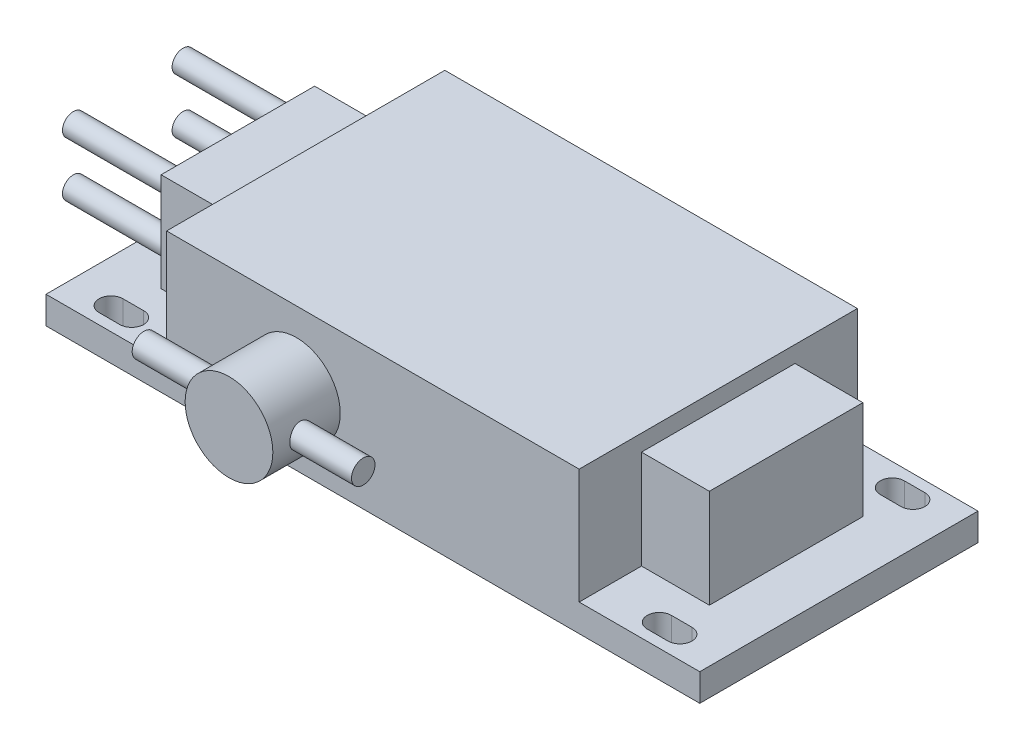
SolidWorks part; units mm, degrees
ref_plane "Спереди" through (0, 0, 0) normal (0, 0, 1) x (1, 0, 0)
ref_plane "Сверху" through (0, 0, 0) normal (0, 1, 0) x (1, 0, 0)
ref_plane "Справа" through (0, 0, 0) normal (1, 0, 0) x (0, 0, -1)
sketch "Sketch1" plane through (0, 0, 0) normal (0, 1, 0) x (1, 0, 0)
  line L0 (107.74, 21.25) -> (111.51, 21.25) construction
  line L1 (0, 25.375) -> (119.25, 25.375)
  line L2 (0, 25.375) -> (0, -25.375)
  line L3 (0, -25.375) -> (119.25, -25.375)
  line L4 (119.25, 25.375) -> (119.25, -25.375)
  line L5 (107.74, 23.435) -> (111.51, 23.435)
  line L6 (107.74, 19.065) -> (111.51, 19.065)
  line L7 (107.74, -21.25) -> (111.51, -21.25) construction
  line L8 (107.74, -19.065) -> (111.51, -19.065)
  line L9 (107.74, -23.435) -> (111.51, -23.435)
  line L10 (7.74, -21.25) -> (11.51, -21.25) construction
  line L11 (7.74, -19.065) -> (11.51, -19.065)
  line L12 (7.74, -23.435) -> (11.51, -23.435)
  line L13 (7.74, 21.25) -> (11.51, 21.25) construction
  line L14 (7.74, 23.435) -> (11.51, 23.435)
  line L15 (7.74, 19.065) -> (11.51, 19.065)
  line L16 (11.51, -21.25) -> (107.74, -21.25) construction
  line L17 (109.625, 21.25) -> (109.625, -21.25) construction
  arc A0 (107.74, 23.435) -> (107.74, 19.065) centre (107.74, 21.25) ccw
  arc A1 (111.51, 19.065) -> (111.51, 23.435) centre (111.51, 21.25) ccw
  arc A2 (107.74, -19.065) -> (107.74, -23.435) centre (107.74, -21.25) ccw
  arc A3 (111.51, -23.435) -> (111.51, -19.065) centre (111.51, -21.25) ccw
  arc A4 (7.74, -19.065) -> (7.74, -23.435) centre (7.74, -21.25) ccw
  arc A5 (11.51, -23.435) -> (11.51, -19.065) centre (11.51, -21.25) ccw
  arc A6 (7.74, 23.435) -> (7.74, 19.065) centre (7.74, 21.25) ccw
  arc A7 (11.51, 19.065) -> (11.51, 23.435) centre (11.51, 21.25) ccw
  point P5 (0, 0)
  point P8 (109.625, 21.25)
  point P13 (109.625, -21.25)
  point P20 (9.625, -21.25)
  point P27 (9.625, 21.25)
  point P36 (59.625, -21.25)
  point P37 (59.625, -25.375)
  point P38 (109.625, 0)
  point P39 (119.25, 0)
  point P42 (5.555, 21.25)
  point P43 (13.695, 21.25)
  dimension "D1" = 119.25
  dimension "D2" = 50.75
  dimension "D3" = 100
  dimension "D4" = 42.5
  dimension "D5" = 4.37
  dimension "D6" = 8.14
extrude "Extrude1" add sketch "Sketch1" along normal blind 5
sketch "Sketch2" plane through (0, 5, 0) normal (0, 1, 0) x (1, 0, 0)
  line L0 (119.25, 25.375) -> (0, 25.375) construction
  line L1 (22, 25.375) -> (97.25, 25.375)
  line L2 (22, 25.375) -> (22, -25.375)
  line L3 (22, -25.375) -> (97.25, -25.375)
  line L4 (97.25, 25.375) -> (97.25, -25.375)
  line L5 (0, -25.375) -> (119.25, -25.375) construction
  line L6 (0, 0) -> (119.25, 0) construction
  line L7 (119.25, -25.375) -> (119.25, 25.375) construction
  line L9 (22, -25.375) -> (97.25, 25.375) construction
  point P14 (59.625, 0)
  point P15 (59.625, 0)
  dimension "D1" = 22
extrude "Extrude2" add sketch "Sketch2" along normal blind 21
sketch "Sketch3" plane through (0, 5, 0) normal (0, 1, 0) x (1, 0, 0)
  line L0 (97.25, 25.375) -> (22, -25.375) construction
  line L1 (109.625, -14) -> (9.625, -14)
  line L2 (109.625, -14) -> (109.625, 14)
  line L3 (109.625, 14) -> (9.625, 14)
  line L4 (9.625, -14) -> (9.625, 14)
  line L5 (109.625, -14) -> (9.625, 14) construction
  point P9 (59.625, 0)
  point P10 (59.625, 0)
  dimension "D1" = 100
  dimension "D2" = 28
extrude "Extrude3" add sketch "Sketch3" along normal blind 18
sketch "Sketch4" plane through (0, 0, 25.375) normal (0, 0, 1) x (1, 0, 0)
  line L0 (45.6774, 0) -> (45.6774, 26) construction
  line L1 (0, 0) -> (119.25, 0) construction
  line L2 (22, 26) -> (97.25, 26) construction
  circle A0 centre (45.6774, 13) radius 8
  point P9 (45.6774, 13)
  dimension "D1" = 16
extrude "Extrude4" add sketch "Sketch4" along normal blind 12.3
sketch "Sketch5" plane through (97.25, 0, 0) normal (1, 0, 0) x (0, 0, -1)
  line L0 (-36.0689, 21) -> (-36.0689, 5) construction
  line L1 (-25.375, 21) -> (-37.675, 21) construction
  line L2 (-37.675, 5) -> (-25.375, 5) construction
  circle A0 centre (-32.4388, 13) radius 2.1441
  point P8 (-36.0689, 13)
extrude "Extrude5" add sketch "Sketch5" along normal blind 20 and the other way blind 20 from offset 52.32 offset against normal yes
sketch "Sketch6" plane through (9.625, 0, 0) normal (-1, 0, 0) x (0, 0, 1)
  line L12 (-10, 9) -> (10, 9)
  line L13 (10, 9) -> (10, 19)
  line L14 (10, 19) -> (-10, 19)
  line L15 (-10, 19) -> (-10, 9)
  line L16 (-10, 9) -> (10, 9) construction
  line L17 (10, 9) -> (10, 19) construction
  line L18 (10, 19) -> (-10, 19) construction
  line L19 (-10, 19) -> (-10, 9) construction
  circle A0 centre (-10, 9) radius 2
  circle A1 centre (-10, 19) radius 2
  circle A2 centre (10, 9) radius 2
  circle A3 centre (10, 19) radius 2
  dimension "D2" = 4
  dimension "D1" = 4
extrude "Extrude6" add sketch "Sketch6" along normal blind 20
